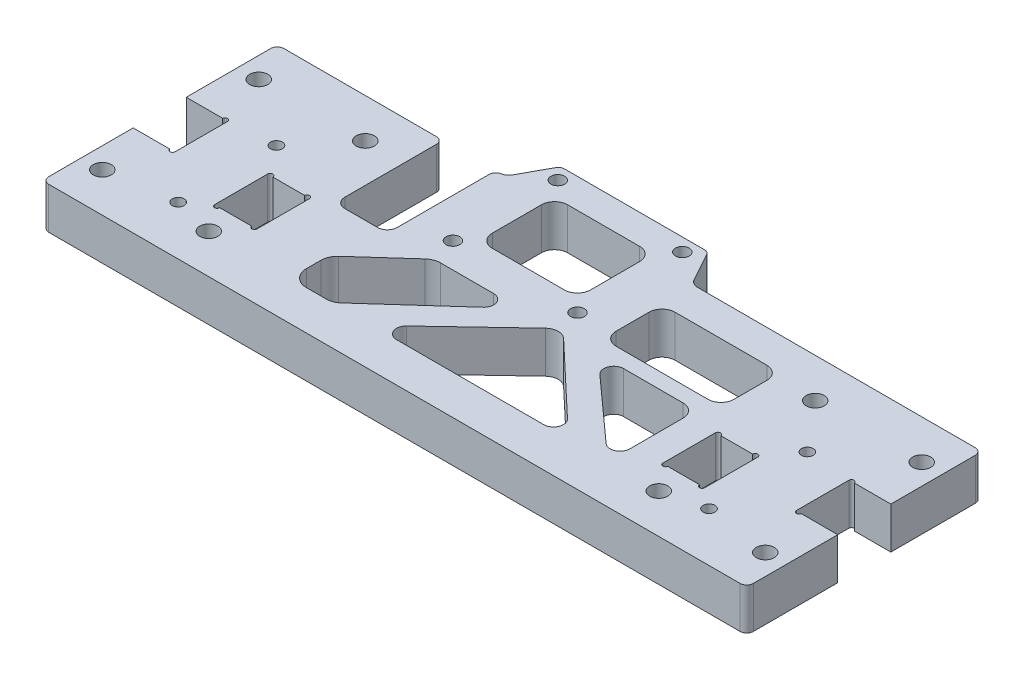
SolidWorks part; units mm, degrees
material "6061 Alloy"
ref_plane "Front Plane" through (0, 0, 0) normal (0, 0, 1) x (1, 0, 0)
ref_plane "Top Plane" through (0, 0, 0) normal (0, 1, 0) x (1, 0, 0)
ref_plane "Right Plane" through (0, 0, 0) normal (1, 0, 0) x (0, 0, -1)
sketch "Sketch1" plane through (0, 0, 0) normal (0, 1, 0) x (1, 0, 0)
  line L0 (107.5, 76.65) -> (107.5, 0) construction
  line L6 (32.7004, 36.1) -> (32.7004, 19.9)
  line L8 (45.6, 36) -> (45.6, 20)
  line L13 (0, 71.75) -> (69.5, 71.75)
  line L14 (69.5, 71.75) -> (75.5, 82.75)
  line L15 (75.5, 82.75) -> (120.5, 82.75)
  line L16 (120.5, 82.75) -> (126.5, 71.75)
  line L17 (126.5, 71.75) -> (215, 71.75)
  line L18 (32.7004, 28) -> (45.6, 28) construction
  line L19 (34.3004, 36.1) -> (44.0063, 36.1)
  line L20 (34.3004, 19.9) -> (44.0063, 19.9)
  line L21 (182.2996, 36.1) -> (182.2996, 19.9)
  line L22 (180.6996, 36.1) -> (170.9937, 36.1)
  line L23 (169.4, 36) -> (169.4, 20)
  line L24 (180.6996, 19.9) -> (170.9937, 19.9)
  line L25 (12.7, 35.875) -> (0, 35.875) construction
  line L29 (12.7, 43.975) -> (12.7, 27.775)
  line L30 (11.1189, 43.975) -> (0, 43.975)
  line L31 (11.1189, 27.775) -> (0, 27.775)
  line L32 (0, 27.775) -> (0, 0)
  line L33 (0, 43.975) -> (0, 71.75)
  line L34 (202.3, 35.875) -> (215, 35.875) construction
  line L35 (215, 43.975) -> (215, 71.75)
  line L36 (215, 27.775) -> (215, 0)
  line L37 (203.8811, 27.775) -> (215, 27.775)
  line L38 (203.8811, 43.975) -> (215, 43.975)
  line L39 (202.3, 43.975) -> (202.3, 27.775)
  line L44 (107.5, 0) -> (215, 0)
  line L46 (107.5, 0) -> (0, 0)
  circle A0 centre (38.85, 59.75) radius 2.75
  circle A5 centre (38.85, 12) radius 2.75
  circle A6 centre (176.15, 59.75) radius 2.75
  circle A7 centre (176.15, 12) radius 2.75
  arc A8 (32.7004, 36.1) -> (34.3004, 36.1) centre (33.5004, 36.1) cw
  arc A9 (45.6, 36) -> (44.0063, 36.1) centre (44.8, 36) ccw
  arc A10 (32.7004, 19.9) -> (34.3004, 19.9) centre (33.5004, 19.9) ccw
  arc A11 (45.6, 20) -> (44.0063, 19.9) centre (44.8, 20) cw
  arc A12 (182.2996, 19.9) -> (180.6996, 19.9) centre (181.4996, 19.9) cw
  arc A13 (182.2996, 36.1) -> (180.6996, 36.1) centre (181.4996, 36.1) ccw
  arc A14 (169.4, 36) -> (170.9937, 36.1) centre (170.2, 36) cw
  arc A15 (169.4, 20) -> (170.9937, 19.9) centre (170.2, 20) ccw
  circle A16 centre (6.35, 12) radius 2.75
  circle A17 centre (6.35, 59.75) radius 2.75
  arc A18 (12.7, 27.775) -> (11.1189, 27.775) centre (11.9095, 27.8976) cw
  arc A19 (12.7, 43.975) -> (11.1189, 43.975) centre (11.9095, 43.8524) ccw
  arc A20 (202.3, 43.975) -> (203.8811, 43.975) centre (203.0905, 43.8524) cw
  arc A21 (202.3, 27.775) -> (203.8811, 27.775) centre (203.0905, 27.8976) ccw
  circle A22 centre (208.65, 59.75) radius 2.75
  circle A23 centre (208.65, 12) radius 2.75
  dimension "D12" = 5.5
  dimension "D16" = 5.5
  dimension "D17" = 0.8
  dimension "D18" = 0.8
  dimension "D19" = 0.8
  dimension "D20" = 0.8
  dimension "D21" = 5.5
  dimension "D22" = 5.5
  dimension "D27" = 0.8
  dimension "D1" = 215
  dimension "D2" = 71.75
  dimension "D5" = 61.9
  dimension "D6" = 12.9
  dimension "D4" = 11
  dimension "D7" = 6
  dimension "D8" = 38
  dimension "D10" = 45
  dimension "D11" = 16.2
  dimension "D14" = 6
  dimension "D13" = 12
  dimension "D25" = 16.2
  dimension "D3" = 12
  dimension "D23" = 16.2
  dimension "D26" = 12.7
extrude "Boss-Extrude1" add sketch "Sketch1" along normal blind 12.7
sketch "Sketch2" plane through (0, 12.7, 0) normal (0, 1, 0) x (1, 0, 0)
  line L1 (50.6, 85.2461) -> (66.6, 85.2461)
  line L2 (50.6, 85.2461) -> (50.6, 38.75)
  line L3 (50.6, 38.75) -> (66.6, 38.75)
  line L4 (66.6, 85.2461) -> (66.6, 38.75)
  line L5 (45.6, 20) -> (45.6, 36) construction
  line L12 (69.5, 71.75) -> (0, 71.75) construction
  dimension "D1" = 5
  dimension "D2" = 16
  dimension "D3" = 33
extrude "Cut-Extrude1" cut sketch "Sketch2" against normal through all
sketch "Sketch3" plane through (0, 12.7, 0) normal (0, 1, 0) x (1, 0, 0)
  line L1 (66.6, 38.75) -> (66.6, 71.75) construction
  line L2 (120.5, 82.75) -> (75.5, 82.75) construction
  circle A0 centre (78.6, 78.75) radius 2.1
  circle A1 centre (78.6, 46.75) radius 2.1
  circle A2 centre (116.6, 78.75) radius 2.1
  circle A3 centre (116.6, 46.75) radius 2.1
  dimension "D2" = 4.2
  dimension "D5" = 4.2
  dimension "D8" = 32
  dimension "D1" = 4
  dimension "D3" = 12
  dimension "D4" = 32
  dimension "D7" = 38
  dimension "D6" = 2
extrude "Cut-Extrude2" cut sketch "Sketch3" against normal through all
sketch "Sketch5" plane through (0, 12.7, 0) normal (0, 1, 0) x (1, 0, 0)
  line L3 (98.7821, 39) -> (82.5187, 39)
  line L11 (78.0261, 13.2835) -> (100.789, 33.7701)
  line L12 (66.6, 38.75) -> (66.6, 71.75) construction
  line L13 (115.8513, 37.7761) -> (94.0759, 17.1795)
  line L14 (118.6, 40.376) -> (118.6, 12) construction
  line L15 (96.1374, 12) -> (141.0626, 12)
  line L16 (121.3487, 37.7761) -> (143.1241, 17.1795)
  line L17 (138.4179, 39) -> (156.6, 39)
  line L18 (155.5931, 16.5062) -> (136.411, 33.7701)
  line L19 (160.6, 35) -> (160.6, 18.7361)
  line L20 (120.5, 82.75) -> (75.5, 82.75) construction
  line L21 (86.6, 73.75) -> (108.6, 73.75)
  line L22 (82.6, 69.75) -> (82.6, 54.75)
  line L23 (86.6, 50.75) -> (108.6, 50.75)
  line L24 (112.6, 69.75) -> (112.6, 54.75)
  line L25 (215, 71.75) -> (126.5, 71.75) construction
  line L26 (131.4, 61.75) -> (159.4, 61.75)
  line L27 (127.4, 57.75) -> (127.4, 47.75)
  line L28 (131.4, 43.75) -> (159.4, 43.75)
  line L29 (163.4, 57.75) -> (163.4, 47.75)
  line L30 (79.1739, 37.7165) -> (65.279, 25.2111)
  line L31 (169.4, 36) -> (169.4, 20) construction
  line L32 (63.6239, 21.4947) -> (63.6239, 17)
  line L33 (68.6239, 12) -> (74.6813, 12)
  arc A0 (121.3487, 37.7761) -> (115.8513, 37.7761) centre (118.6, 34.8701) ccw
  arc A1 (160.6, 35) -> (156.6, 39) centre (156.6, 35) ccw
  arc A3 (112.6, 69.75) -> (108.6, 73.75) centre (108.6, 69.75) ccw
  arc A4 (108.6, 50.75) -> (112.6, 54.75) centre (108.6, 54.75) ccw
  arc A5 (82.6, 54.75) -> (86.6, 50.75) centre (86.6, 54.75) ccw
  arc A6 (82.6, 69.75) -> (86.6, 73.75) centre (86.6, 69.75) cw
  arc A7 (155.5931, 16.5062) -> (160.6, 18.7361) centre (157.6, 18.7361) ccw
  arc A8 (136.411, 33.7701) -> (138.4179, 39) centre (138.4179, 36) cw
  arc A10 (141.0626, 12) -> (143.1241, 17.1795) centre (141.0626, 15) ccw
  arc A11 (96.1374, 12) -> (94.0759, 17.1795) centre (96.1374, 15) cw
  arc A12 (100.789, 33.7701) -> (98.7821, 39) centre (98.7821, 36) ccw
  arc A13 (163.4, 57.75) -> (159.4, 61.75) centre (159.4, 57.75) ccw
  arc A14 (159.4, 43.75) -> (163.4, 47.75) centre (159.4, 47.75) ccw
  arc A15 (127.4, 47.75) -> (131.4, 43.75) centre (131.4, 47.75) ccw
  arc A16 (127.4, 57.75) -> (131.4, 61.75) centre (131.4, 57.75) cw
  arc A17 (79.1739, 37.7165) -> (82.5187, 39) centre (82.5187, 34) cw
  arc A18 (63.6239, 21.4947) -> (65.279, 25.2111) centre (68.6239, 21.4947) cw
  arc A19 (68.6239, 12) -> (63.6239, 17) centre (68.6239, 17) cw
  arc A20 (74.6813, 12) -> (78.0261, 13.2835) centre (74.6813, 17) ccw
  point P25 (160.6, 39)
  point P33 (112.6, 50.75)
  point P36 (82.6, 50.75)
  point P39 (82.6, 73.75)
  point P42 (160.6, 12)
  point P45 (130.6, 39)
  point P48 (76.6, 12)
  point P51 (148.6, 12)
  point P54 (88.6, 12)
  point P57 (106.6, 39)
  point P68 (163.4, 61.75)
  point P71 (163.4, 43.75)
  point P76 (127.4, 61.75)
  dimension "D11" = 4
  dimension "D12" = 3
  dimension "D13" = 3
  dimension "D14" = 3
  dimension "D19" = 4
  dimension "D2" = 5
  dimension "D4" = 5
  dimension "D3" = 12
  dimension "D6" = 30
  dimension "D7" = 9
  dimension "D8" = 16
  dimension "D9" = 23
  dimension "D10" = 30
  dimension "D15" = 10
  dimension "D16" = 18
  dimension "D17" = 6
  dimension "D18" = 36
extrude "Cut-Extrude3" cut sketch "Sketch5" against normal through all
fillet "Fillet1" radius 3 4 edges at (69.5, 6.35, -71.75) (66.6, 6.35, -38.75) (50.6, 6.35, -38.75) (126.5, 6.35, -71.75)
fillet "Fillet2" radius 2 8 edges at (215, 6.35, -71.75) (120.5, 6.35, -82.75) (75.5, 6.35, -82.75) (50.6, 6.35, -71.75) (66.6, 6.35, -71.75) (0, 6.35, -71.75) (215, 6.35, 0) (0, 6.35, 0)
sketch "Sketch6" plane through (0, 12.7, 0) normal (0, 1, 0) x (1, 0, 0)
  line L0 (2, 0) -> (213, 0) construction
  line L1 (107.5, 92.584) -> (107.5, -38.973) construction
  line L2 (215, 2) -> (215, 27.775) construction
  circle A0 centre (188.5, 45) radius 1.8
  circle A1 centre (176.15, 59.75) radius 2.75 construction
  circle A2 centre (188.5, 15) radius 1.8
  circle A3 centre (26.5, 45) radius 1.8
  circle A4 centre (26.5, 15) radius 1.8
  dimension "D2" = 3.6
  dimension "D5" = 3.6
  dimension "D1" = 12.35
  dimension "D3" = 45
  dimension "D4" = 15
  dimension "D6" = 107.5
extrude "Cut-Extrude4" cut sketch "Sketch6" against normal through all
equation "\"DriveMotorLength\"= 90mm"
equation "\"DriveMotorGap\"= 10mm"
equation "\"AluminumThickness\"= 0.5in"
equation "\"ChassisWidth\"= ( \"DriveMotorLength\" + \"AluminumThickness\" ) * 2 + \"DriveMotorGap\""
equation "\"RepeatMagnumHoleWidth\"= 19.05mm"
equation "\"MortiseWidth\"= 16mm"
equation "\"ChassisScrewThruHole\"= 5.5mm"
equation "\"D11@Sketch1\"=\"MortiseSlotWidth\""
equation "\"D12@Sketch1\"=\"ChassisScrewThruHole\""
equation "\"D16@Sketch1\"=\"ChassisScrewThruHole\""
equation "\"MortiseSlotWidth\"= 16.2mm"
equation "\"Dogbone\"= 0.8mm"
equation "\"D17@Sketch1\"=\"Dogbone\""
equation "\"D18@Sketch1\"=\"Dogbone\""
equation "\"D19@Sketch1\"=\"Dogbone\""
equation "\"D20@Sketch1\"=\"Dogbone\""
equation "\"D21@Sketch1\"=\"ChassisScrewThruHole\""
equation "\"D22@Sketch1\"=\"ChassisScrewThruHole\""
equation "\"D27@Sketch1\"=\"Dogbone\""
equation "\"D23@Sketch1\"=\"MortiseSlotWidth\""
equation "\"D25@Sketch1\"=\"MortiseSlotWidth\""
